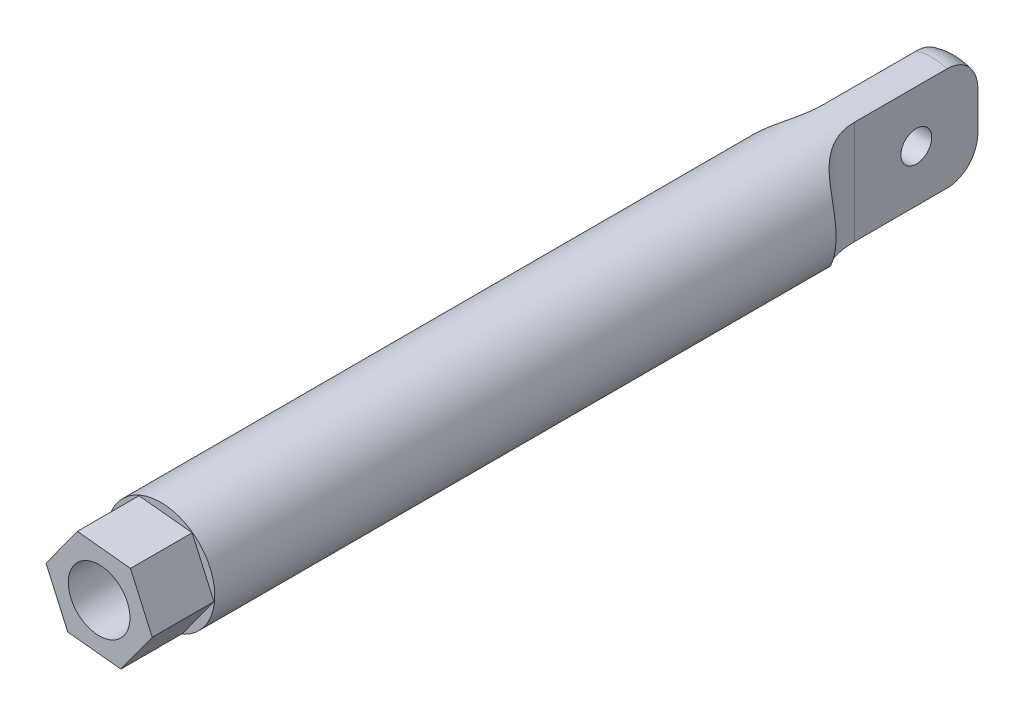
SolidWorks part; units mm, degrees
ref_plane "Front Plane" through (0, 0, 0) normal (0, 0, 1) x (1, 0, 0)
ref_plane "Top Plane" through (0, 0, 0) normal (0, 1, 0) x (1, 0, 0)
ref_plane "Right Plane" through (0, 0, 0) normal (1, 0, 0) x (0, 0, -1)
sketch "Sketch2" plane through (0, 0, 0) normal (0, 0, 1) x (1, 0, 0)
  circle A1 centre (0, 0) radius 1.75
  dimension "D1" = 3.5
extrude "Boss-Extrude1" add sketch "Sketch2" along normal blind 20
sketch "Sketch3" plane through (0, 0, 0) normal (0, 0, -1) x (-1, 0, 0)
  line L0 (0, -4.4665) -> (0, 4.3289) construction
  line L1 (0.5, 1.6771) -> (0.5, -1.6771)
  line L2 (-0.5, 1.6771) -> (-0.5, -1.6771)
  circle A0 centre (0, 0) radius 1.75 construction
  arc A1 (-0.5, -1.6771) -> (0.5, -1.6771) centre (0, 0) ccw
  arc A2 (0.5, 1.6771) -> (-0.5, 1.6771) centre (0, 0) ccw
  dimension "D1" = 0.5
extrude "Boss-Extrude2" add sketch "Sketch3" along normal blind 6
sketch "Sketch4" plane through (0.5, 0, 0) normal (1, 0, 0) x (0, 0, -1)
  line L0 (6, 1.6771) -> (6, -1.6771) construction
  circle A0 centre (4, 0) radius 0.5
  dimension "D2" = 1
  dimension "D1" = 2
extrude "Cut-Extrude1" cut sketch "Sketch4" against normal through all both and the other way through all
sketch "Sketch5" plane through (0, 0, 20) normal (0, 0, 1) x (1, 0, 0)
  line L1 (0.7059, -1.5817) -> (1.7227, -0.1796)
  line L2 (1.7227, -0.1796) -> (1.0169, 1.4021)
  line L3 (1.0169, 1.4021) -> (-0.7059, 1.5817)
  line L4 (-0.7059, 1.5817) -> (-1.7227, 0.1796)
  line L5 (-1.7227, 0.1796) -> (-1.0169, -1.4021)
  line L6 (-1.0169, -1.4021) -> (0.7059, -1.5817)
  circle A0 centre (0, 0) radius 1
  circle A1 centre (0, 0) radius 1.5 construction
  dimension "D1" = 2
  dimension "D2" = 3
extrude "Boss-Extrude3" add sketch "Sketch5" along normal blind 2
sketch "Sketch6" plane through (0, 0, 20) normal (0, 0, 1) x (1, 0, 0)
  circle A1 centre (0, 0) radius 1
  circle A2 centre (0, 0) radius 1
  dimension "D1" = 0
extrude "Cut-Extrude2" cut sketch "Sketch6" against normal blind 15
fillet "Fillet5" radius 1 2 edges at (0, -1.75, -6) (0, 1.75, -6)
fillet "Fillet6" radius 2 2 edges
